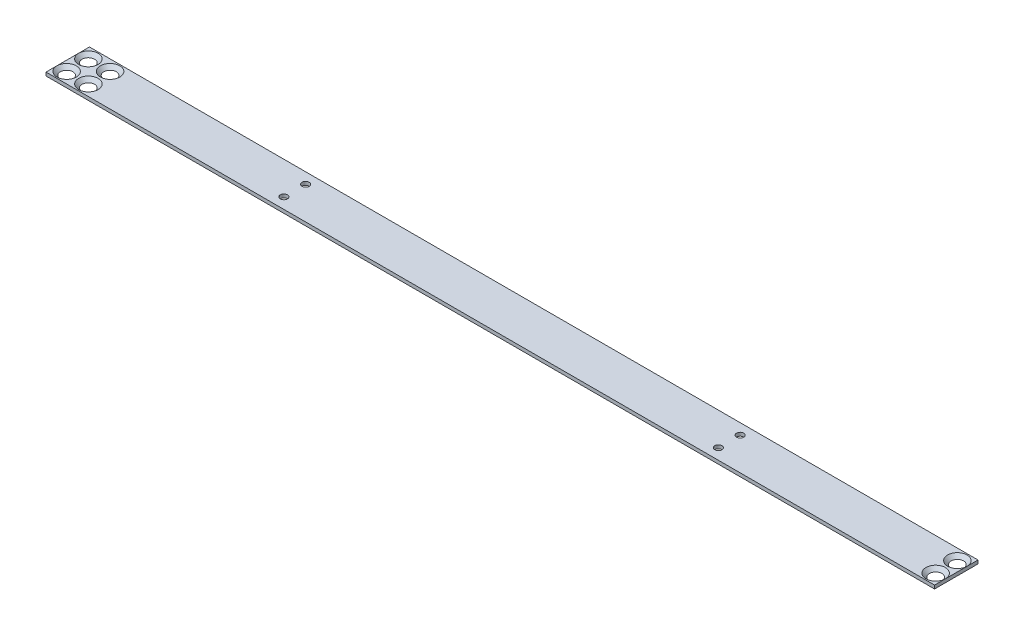
SolidWorks part; units mm, degrees
ref_plane "Front Plane" through (0, 0, 0) normal (0, 0, 1) x (1, 0, 0)
ref_plane "Top Plane" through (0, 0, 0) normal (0, 1, 0) x (1, 0, 0)
ref_plane "Right Plane" through (0, 0, 0) normal (1, 0, 0) x (0, 0, -1)
sketch "Sketch1" plane through (0, 0, 0) normal (0, 1, 0) x (1, 0, 0)
  line L1 (-204.5, -10) -> (204.5, -10)
  line L2 (-204.5, -10) -> (-204.5, 10)
  line L3 (-204.5, 10) -> (204.5, 10)
  line L4 (204.5, -10) -> (204.5, 10)
  line L5 (-204.5, -10) -> (204.5, 10) construction
  line L6 (-204.5, 10) -> (204.5, -10) construction
  point P0 (0, 0)
  dimension "D1" = 409
  dimension "D2" = 20
extrude "Boss-Extrude1" add sketch "Sketch1" along normal blind 1.5875
hole_wizard "CSK for M4 SFHCS1" positions "Sketch2" profile "Sketch4" countersink size "M4" standard "ANSI Metric" end condition through all
sketch "Sketch2" plane through (0, 1.5875, 0) normal (0, 1, 0) x (1, 0, 0)
  line L1 (-200, -5) -> (-190, -5)
  line L2 (-200, -5) -> (-200, 5)
  line L3 (-200, 5) -> (-190, 5)
  line L4 (-190, -5) -> (-190, 5)
  line L5 (-200, -5) -> (-190, 5) construction
  line L6 (-200, 5) -> (-190, -5) construction
  line L7 (-204.5, 10) -> (-204.5, -10) construction
  line L8 (200, 5) -> (200, -5)
  line L10 (204.5, -10) -> (204.5, 10) construction
  point P2 (-190, 5)
  point P61 (-200, -5)
  point P62 (-200, 5)
  point P63 (-190, -5)
  point P67 (-195, 0)
  point P69 (200, 5)
  point P70 (200, -5)
  point P75 (200, 0)
  dimension "D1" = 10
  dimension "D2" = 4.5
  dimension "D3" = 10
  dimension "D4" = 4.5
sketch "Sketch4" plane through (-190, 1.5875, -5) normal (1, 0, 0) x (0, 0, 1)
  line L0 (0, 0) -> (0, 1.5875)
  line L1 (0, 1.5875) -> (2.25, 1.5875)
  line L2 (2.25, 1.5875) -> (2.25, 2.23)
  line L3 (2.25, 2.23) -> (4.48, 0)
  line L5 (4.48, 0) -> (0, 0)
  line L6 (-2.25, 2.23) -> (-4.48, 0) construction
  line L11 (0, -6.35) -> (0, 107.95) construction
  dimension "Thru Hole Dia." = 4.5
  dimension "Thru Hole Depth" = 1.5875
  dimension "Near C'Sink Dia." = 8.96
  dimension "Near C'Sink Angle" = 90
hole_wizard "M4x0.7 Tapped Hole1" positions "Sketch5" profile "Sketch7" tap size "M4x0.7" standard "ANSI Metric" end condition through all
sketch "Sketch5" plane through (0, 1.5875, 0) normal (0, 1, 0) x (1, 0, 0)
  line L1 (-100, -5) -> (100, -5)
  line L2 (-100, -5) -> (-100, 5)
  line L3 (-100, 5) -> (100, 5)
  line L4 (100, -5) -> (100, 5)
  line L5 (-100, -5) -> (100, 5) construction
  line L6 (-100, 5) -> (100, -5) construction
  point P2 (100, 5)
  point P45 (-100, -5)
  point P46 (-100, 5)
  point P47 (100, -5)
  point P52 (0, 0)
  dimension "D1" = 10
  dimension "D2" = 200
sketch "Sketch7" plane through (100, 1.5875, -5) normal (1, 0, 0) x (0, 0, 1)
  line L0 (0, 0) -> (0, 1.5875)
  line L1 (0, 1.5875) -> (1.65, 1.5875)
  line L2 (1.65, 1.5875) -> (1.65, 0)
  line L5 (1.65, 0) -> (0, 0)
  line L11 (0, -6.35) -> (0, 107.95) construction
  dimension "Thru Tap Drill Dia." = 3.3
  dimension "Thru Tap Drill Depth" = 1.5875
cosmetic thread "Hole Thread1" parameters "D2"=4
cosmetic thread "Hole Thread2" parameters "D2"=4
cosmetic thread "Hole Thread3" parameters "D2"=4
cosmetic thread "Hole Thread4" parameters "D2"=4
